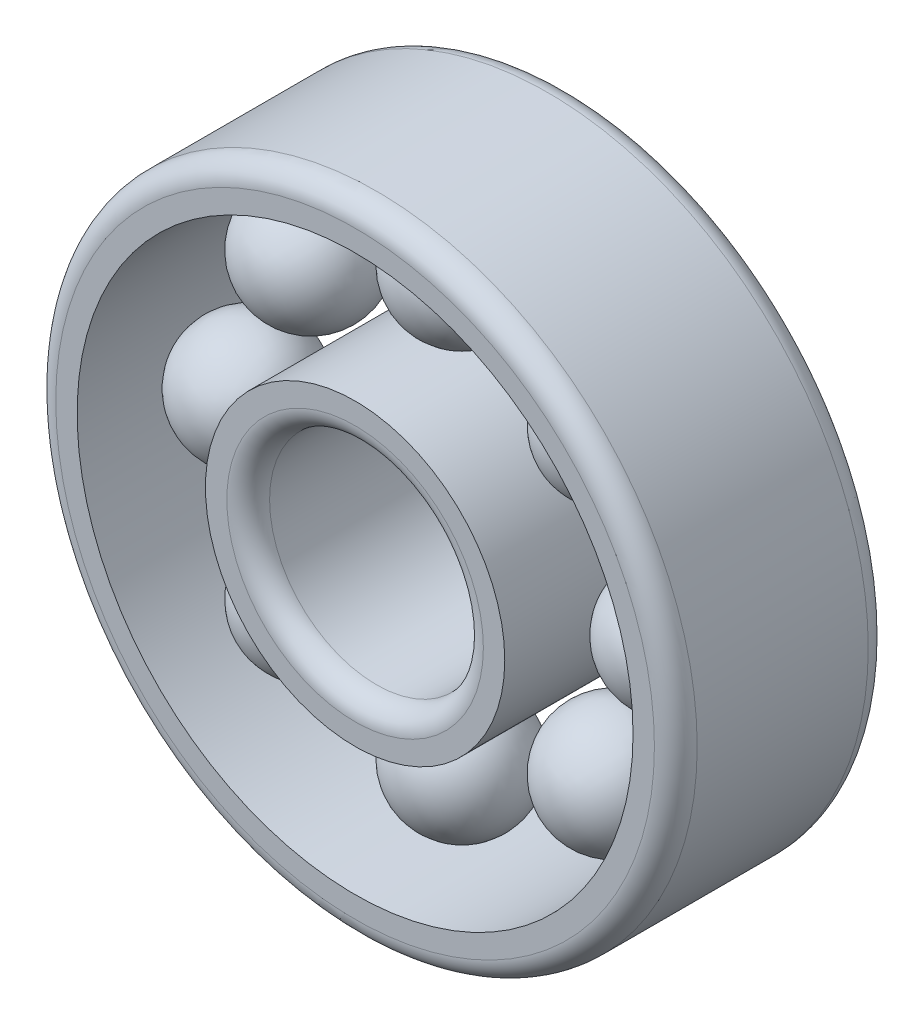
SolidWorks part; units mm, degrees
ref_plane "Front Plane" through (0, 0, 0) normal (0, 0, 1) x (1, 0, 0)
ref_plane "Top Plane" through (0, 0, 0) normal (0, 1, 0) x (1, 0, 0)
ref_plane "Right Plane" through (0, 0, 0) normal (1, 0, 0) x (0, 0, -1)
sketch "S" plane through (0, 0, 0) normal (0, 0, 1) x (1, 0, 0)
  line L0 (-0.5, 0) -> (0.5, 0) construction
  circle A0 centre (0, 0) radius 0.5 construction
  circle A1 centre (0, 0) radius 1.5 construction
  circle A2 centre (0, 0) radius 0.7 construction
  circle A3 centre (0, 0) radius 1.3 construction
  dimension "ID" = 1
  dimension "OD" = 3
  dimension "IDa" = 1.4
  dimension "ODa" = 2.6
  dimension "B" = 1
ref_axis "Z" through (0, 0, -0.55) along (0, 0, 1)
sketch "InnerS" plane through (0, 0, 0) normal (0, 1, 0) x (1, 0, 0)
  line L0 (0.5, -0.5) -> (0.7, -0.5)
  line L1 (0.7, -0.5) -> (0.7, 0.5)
  line L2 (0.7, 0.5) -> (0.5, 0.5)
  line L3 (0.5, 0.5) -> (0.5, -0.5)
  line L4 (0, -1.75) -> (0, 1.75) construction
  dimension "r1" = 0.5
  dimension "r2" = 0.7
  dimension "z1" = 0.5
  dimension "z2" = 0.5
revolve "InnerRing" add sketch "InnerS" angle 360 about L4
sketch "OuterS" plane through (0, 0, 0) normal (0, 1, 0) x (1, 0, 0)
  line L0 (1.3, -0.5) -> (1.5, -0.5)
  line L1 (1.5, -0.5) -> (1.5, 0.5)
  line L2 (1.5, 0.5) -> (1.3, 0.5)
  line L3 (1.3, 0.5) -> (1.3, -0.5)
  line L4 (0, -1.75) -> (0, 1.75) construction
  dimension "r1" = 1.3
  dimension "r2" = 1.5
  dimension "z1" = 0.5
  dimension "z2" = 0.5
revolve "OuterRing" add sketch "OuterS" angle 360 about L4
sketch "BallS" plane through (0, 0, 0) normal (0, 1, 0) x (1, 0, 0)
  line L0 (0.715, 0) -> (1.285, 0)
  arc A0 (0.715, 0) -> (1.285, 0) centre (1, 0) ccw
  dimension "r" = 0.285
  dimension "p" = 1
revolve "Ball" add sketch "BallS" angle 360 about L0
pattern_circular "BallsPattern" count 8 over 360 about axis through (0, 0, -0.55) along (0, 0, 1) of bodies 103
fillet "F1" radius 0.1 2 edges at (1.5, 0, -0.5) (1.5, 0, 0.5)
fillet "F2" radius 0.1 2 edges at (0.5, 0, -0.5) (0.5, 0, 0.5)
equation "\"r1@InnerS\" = abs(0.5*\"ID@S\")"
equation "\"r2@InnerS\" = abs(0.5*\"IDa@S\")"
equation "\"z1@InnerS\" = abs(-0.5*\"B@S\")"
equation "\"z2@InnerS\" = abs(0.5*\"B@S\")"
equation "\"r1@OuterS\" = abs(0.5*\"ODa@S\")"
equation "\"r2@OuterS\" = abs(0.5*\"OD@S\")"
equation "\"z1@OuterS\" = abs(-0.5*\"B@S\")"
equation "\"z2@OuterS\" = abs(0.5*\"B@S\")"
equation "\"r@BallS\" = abs(0.2375*\"ODa@S\"-0.2375*\"IDa@S\")"
equation "\"p@BallS\" = abs(0.25*\"IDa@S\"+0.25*\"ODa@S\")"
equation "\"N@BallsPattern\" = int(2.417*(0.25*\"IDa@S\"+0.25*\"ODa@S\")/(0.2375*\"ODa@S\"-0.2375*\"IDa@S\"))"
equation "\"r_min@F2\" = \"r_min@F1\""
